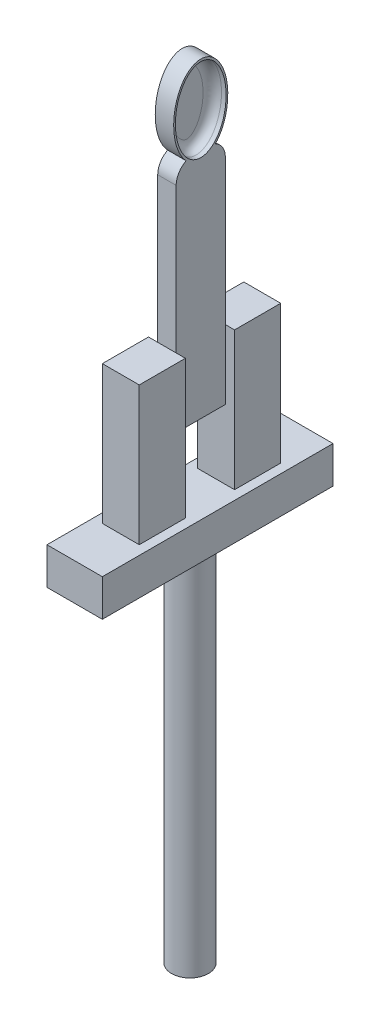
SolidWorks part; units mm, degrees
ref_plane "Front Plane" through (0, 0, 0) normal (0, 0, 1) x (1, 0, 0)
ref_plane "Top Plane" through (0, 0, 0) normal (0, 1, 0) x (1, 0, 0)
ref_plane "Right Plane" through (0, 0, 0) normal (1, 0, 0) x (0, 0, -1)
sketch "Sketch1" plane through (0, 0, 0) normal (0, 1, 0) x (1, 0, 0)
  circle A0 centre (0, 0) radius 10
  dimension "D1" = 20
extrude "Boss-Extrude1" add sketch "Sketch1" along normal blind 200
sketch "Sketch2" plane through (0, 0, 0) normal (1, 0, 0) x (0, 0, -1)
  line L0 (0, 200) -> (0, 210) construction
  line L1 (10, 200) -> (-10, 200) construction
  line L3 (-62.5, 220) -> (62.5, 220)
  line L4 (-62.5, 220) -> (-62.5, 200)
  line L5 (-62.5, 200) -> (62.5, 200)
  line L6 (62.5, 220) -> (62.5, 200)
  line L7 (-62.5, 220) -> (62.5, 200) construction
  line L8 (-62.5, 200) -> (62.5, 220) construction
  dimension "D1" = 10
  dimension "D2" = 125
extrude "Boss-Extrude2" add sketch "Sketch2" along normal blind 15 and the other way blind 15
sketch "Sketch3" plane through (0, 0, 0) normal (1, 0, 0) x (0, 0, -1)
  line L0 (-62.5, 220) -> (-37.5, 220) construction
  line L9 (62.5, 220) -> (-62.5, 220) construction
  line L10 (62.5, 220) -> (39.1488, 220) construction
  line L12 (-37.5, 220) -> (-12.5, 220)
  line L13 (-37.5, 220) -> (-37.5, 295)
  line L14 (-37.5, 295) -> (-12.5, 295)
  line L15 (-12.5, 220) -> (-12.5, 295)
  line L16 (39.1488, 220) -> (14.1488, 220)
  line L17 (39.1488, 220) -> (39.1488, 295)
  line L18 (39.1488, 295) -> (14.1488, 295)
  line L19 (14.1488, 220) -> (14.1488, 295)
  dimension "D1" = 25
  dimension "D2" = 25
  dimension "D3" = 75
  dimension "D4" = 75
ref_axis "Axis1" through (0, 200, 0) along (0, -1, 0)
extrude "Boss-Extrude3" add sketch "Sketch3" along normal blind 10 and the other way blind 10
sketch "Sketch5" plane through (0, 0, 0) normal (1, 0, 0) x (0, 0, -1)
  line L0 (-12.5, 257.5) -> (14.1488, 257.5) construction
  line L1 (-12.5, 220) -> (-12.5, 295) construction
  line L2 (14.1488, 295) -> (14.1488, 220) construction
  line L4 (-12.5, 257.5) -> (14.1488, 257.5)
  line L5 (-12.5, 257.5) -> (-12.5, 382.5)
  line L6 (-12.5, 382.5) -> (14.1488, 382.5)
  line L7 (14.1488, 257.5) -> (14.1488, 382.5)
  dimension "D1" = 125
extrude "Boss-Extrude4" add sketch "Sketch5" along normal blind 5 and the other way blind 5
sketch "Sketch6" plane through (0, 0, 0) normal (1, 0, 0) x (0, 0, -1)
  line L0 (0.8244, 382.5) -> (0.8244, 402.5) construction
  line L2 (14.1488, 382.5) -> (-12.5, 382.5) construction
  line L401 (0.8244, 378.7204) -> (0.8244, 426.2796) construction
  line L402 (15.4837, 402.5) -> (-13.8349, 402.5) construction
  ellipse E0 centre (0.8244, 402.5) end of major axis (0.8244, 378.7204) minor radius 14.6593
  dimension "D1" = 20
extrude "Boss-Extrude5" add sketch "Sketch6" along normal blind 5 and the other way blind 5
fillet "Fillet1" radius 10 1 edges at (0, 382.5, -14.1488)
fillet "Fillet2" radius 10 1 edges at (0, 382.5, 12.5)
sketch "Sketch7" plane through (5, 0, 0) normal (1, 0, 0) x (0, 0, -1)
  line L0 (-13.8349, 402.5) -> (15.4837, 402.5) construction
  line L315 (0.8244, 425) -> (0.8244, 380) construction
  line L316 (-12.9256, 402.5) -> (14.5744, 402.5) construction
  ellipse E0 centre (0.8244, 402.5) end of major axis (0.8244, 378.7204) minor radius 14.6593 (8.7543, 382.5) -> (-7.1055, 382.5) ccw construction
  ellipse E1 centre (0.8244, 402.5) end of major axis (0.8244, 425) minor radius 13.75
  dimension "D1" = 45
  dimension "D2" = 27.5
extrude "Cut-Extrude1" cut sketch "Sketch7" against normal blind 7.5
fillet "Fillet3" radius 5 1 edges at (-2.5, 425, -0.8244)
ref_plane "Plane1" through (0, 100, 0) normal (0, 1, 0) x (1, 0, 0)
ref_axis "Axis2" through (-16.5, 100, 0) along (1, 0, 0)
ref_axis "Axis4" through (0, 100, 68.75) along (0, 0, -1)
